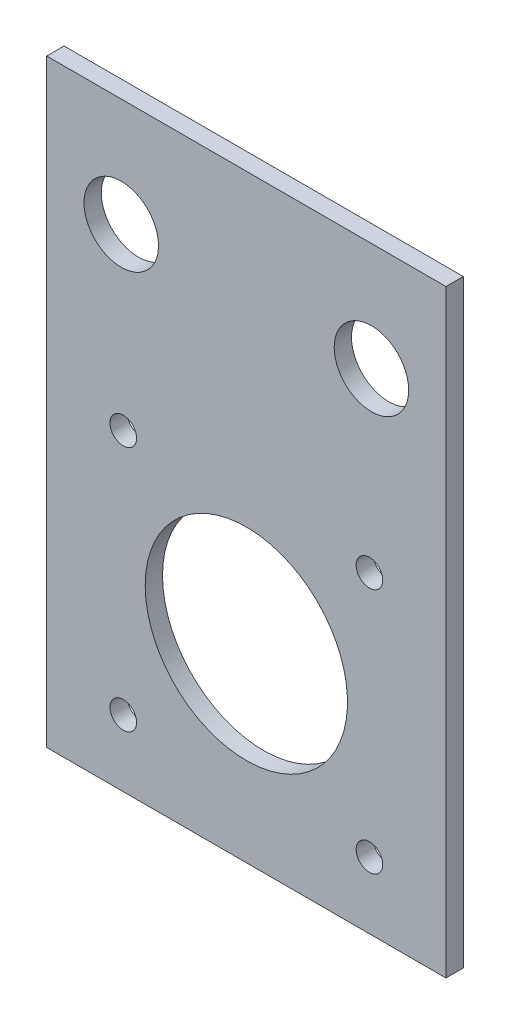
SolidWorks part; units mm, degrees
ref_plane "Front Plane" through (0, 0, 0) normal (0, 0, 1) x (1, 0, 0)
ref_plane "Top Plane" through (0, 0, 0) normal (0, 1, 0) x (1, 0, 0)
ref_plane "Right Plane" through (0, 0, 0) normal (1, 0, 0) x (0, 0, -1)
sketch "Sketch1" plane through (0, 0, 0) normal (0, 0, 1) x (1, 0, 0)
  line L0 (38.1, 114.3) -> (38.1, 0) construction
  line L1 (0, 0) -> (76.2, 0)
  line L2 (0, 0) -> (0, 114.3)
  line L3 (0, 114.3) -> (76.2, 114.3)
  line L4 (76.2, 0) -> (76.2, 114.3)
  line L5 (38.1, 12.7) -> (61.595, 12.7) construction
  line L6 (38.1, 12.7) -> (38.1, 36.195) construction
  line L7 (38.1, 36.195) -> (0, 36.195) construction
  line L8 (38.1, 114.3) -> (38.1, 93.599) construction
  line L9 (38.1, 93.599) -> (14.224, 93.599) construction
  circle A0 centre (61.595, 12.7) radius 2.54
  circle A1 centre (61.595, 59.69) radius 2.54
  circle A2 centre (14.605, 12.7) radius 2.54
  circle A3 centre (14.605, 59.69) radius 2.54
  circle A4 centre (14.224, 93.599) radius 7.112
  circle A5 centre (61.976, 93.599) radius 7.112
  circle A6 centre (38.1, 36.195) radius 19.304
  point P10 (38.1, 12.7)
  point P13 (38.1, 36.195)
  point P22 (38.1, 93.599)
  dimension "D2" = 46.99
  dimension "D1" = 12.7
  dimension "D3" = 46.99
extrude "Boss-Extrude1" add sketch "Sketch1" along normal blind 3.302
